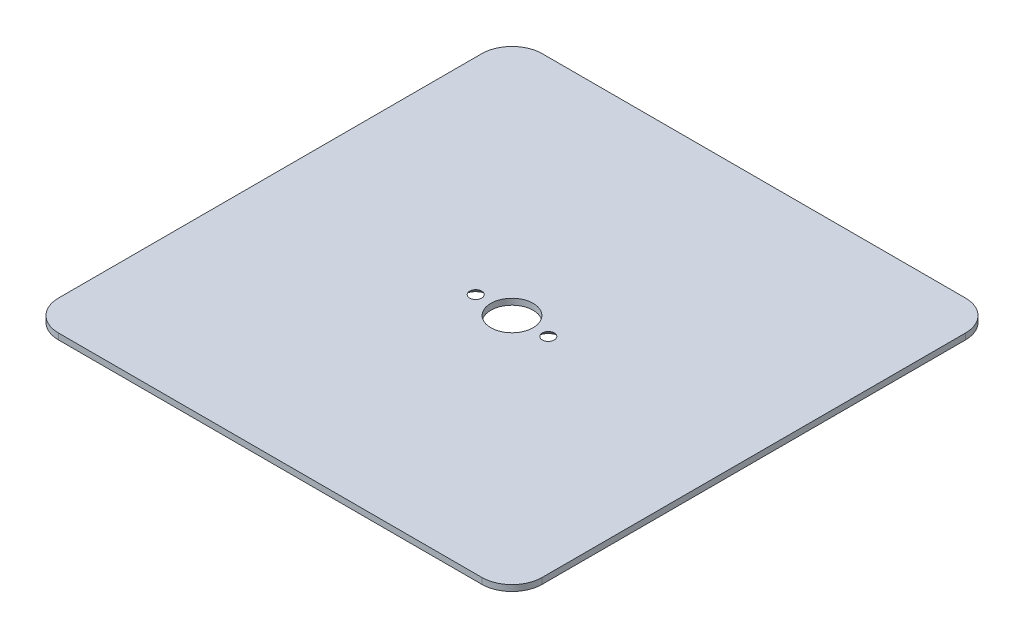
SolidWorks part; units mm, degrees
ref_plane "Plan de face" through (0, 0, 0) normal (0, 0, 1) x (1, 0, 0)
ref_plane "Plan de dessus" through (0, 0, 0) normal (0, 1, 0) x (1, 0, 0)
ref_plane "Plan de droite" through (0, 0, 0) normal (1, 0, 0) x (0, 0, -1)
sketch "Esquisse1" plane through (0, 0, 0) normal (0, 1, 0) x (1, 0, 0)
  line L1 (0, 0) -> (80, 0)
  line L2 (0, 0) -> (0, 80)
  line L3 (0, 80) -> (80, 80)
  line L4 (80, 0) -> (80, 80)
  dimension "D1" = 80
  dimension "D2" = 80
extrude "Extrusion1" add sketch "Esquisse1" along normal blind 1
fillet "Congé1" radius 5 4 edges at (0, 0.5, -80) (0, 0.5, 0) (80, 0.5, -80) (80, 0.5, 0)
sketch "Esquisse2" plane through (0, 0, 0) normal (0, -1, 0) x (1, 0, 0)
  line L0 (0, -75) -> (0, -5) construction
  line L1 (5, 0) -> (75, 0) construction
  circle A0 centre (40, -40) radius 3.5
  dimension "D1" = 7
  dimension "D2" = 40
  dimension "D3" = 40
extrude "Enlèv. mat.-Extru.1" cut sketch "Esquisse2" against normal through all
sketch "Esquisse3" plane through (0, 1, 0) normal (0, 1, 0) x (1, 0, 0)
  line L0 (5, 0) -> (75, 0) construction
  circle A0 centre (34, 40) radius 1
  dimension "D1" = 2
  dimension "D2" = 6
  dimension "D3" = 40
extrude "Enlèv. mat.-Extru.2" cut sketch "Esquisse3" against normal through all
pattern_circular "Répétition circulaire1" count 2 every 180 about axis through (40, 1, -40) along (0, -1, 0) of "Enlèv. mat.-Extru.2"
chamfer "Chanfrein1" distance 1 angle 45 2 edges at (34, 0, -39) (46, 0, -41)
